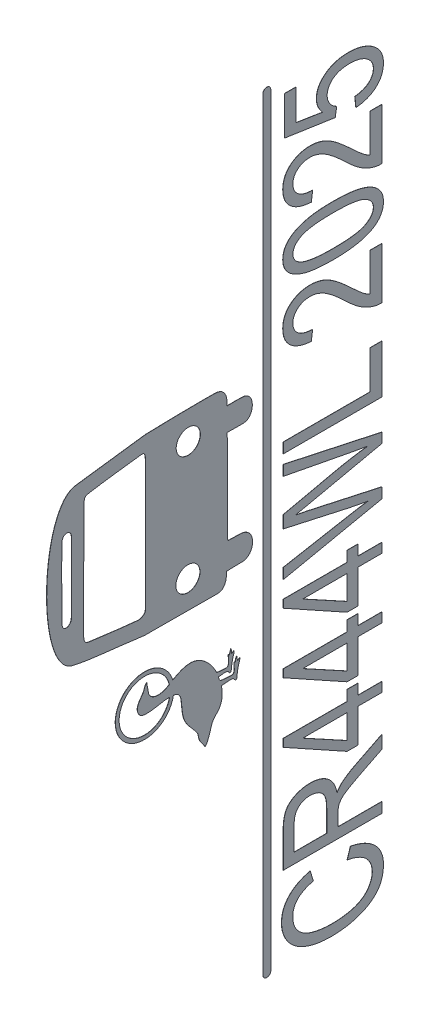
SolidWorks part; units mm, degrees
material "Blue Steel"
ref_plane "Front Plane" through (0, 0, 0) normal (1, 0, 0) x (0, 1, 0)
ref_plane "Top Plane" through (0, 0, 0) normal (0, 0, 1) x (0, 1, 0)
ref_plane "Right Plane" through (0, 0, 0) normal (0, 1, 0) x (-1, 0, 0)
sketch "Sketch3" plane through (0, 0, 0) normal (1, 0, 0) x (0, 1, 0)
  line L0 (443.7564, 375.9378) -> (444.3267, 377.8364)
  line L1 (444.3267, 377.8364) -> (445.1074, 379.6689)
  line L2 (445.1074, 379.6689) -> (446.0917, 381.4354)
  line L3 (446.0917, 381.4354) -> (447.2727, 383.1363)
  line L4 (447.2727, 383.1363) -> (448.6434, 384.7715)
  line L5 (448.6434, 384.7715) -> (450.197, 386.3415)
  line L6 (450.197, 386.3415) -> (451.9266, 387.8462)
  line L7 (451.9266, 387.8462) -> (453.8253, 389.2861)
  line L8 (453.8253, 389.2861) -> (458.1022, 391.9717)
  line L9 (458.1022, 391.9717) -> (462.9727, 394.3999)
  line L10 (462.9727, 394.3999) -> (468.3816, 396.5722)
  line L11 (468.3816, 396.5722) -> (474.2737, 398.4903)
  line L12 (474.2737, 398.4903) -> (480.5938, 400.1558)
  line L13 (480.5938, 400.1558) -> (487.2868, 401.5701)
  line L14 (487.2868, 401.5701) -> (494.2975, 402.7349)
  line L15 (494.2975, 402.7349) -> (501.5707, 403.6517)
  line L16 (501.5707, 403.6517) -> (509.0512, 404.3222)
  line L17 (509.0512, 404.3222) -> (516.684, 404.748)
  line L18 (516.684, 404.748) -> (524.4137, 404.9305)
  line L19 (524.4137, 404.9305) -> (532.1853, 404.8715)
  line L20 (532.1853, 404.8715) -> (539.9436, 404.5724)
  line L21 (539.9436, 404.5724) -> (547.6333, 404.0348)
  line L22 (547.6333, 404.0348) -> (555.1994, 403.2604)
  line L23 (555.1994, 403.2604) -> (562.5866, 402.2507)
  line L24 (562.5866, 402.2507) -> (569.7399, 401.0073)
  line L25 (569.7399, 401.0073) -> (576.6039, 399.5318)
  line L26 (576.6039, 399.5318) -> (583.1236, 397.8257)
  line L27 (583.1236, 397.8257) -> (589.2437, 395.8906)
  line L28 (589.2437, 395.8906) -> (594.9092, 393.7282)
  line L29 (594.9092, 393.7282) -> (600.0648, 391.34)
  line L30 (600.0648, 391.34) -> (604.6553, 388.7276)
  line L31 (604.6553, 388.7276) -> (608.6256, 385.8925)
  line L32 (608.6256, 385.8925) -> (610.361, 384.3919)
  line L33 (610.361, 384.3919) -> (611.9206, 382.8363)
  line L34 (611.9206, 382.8363) -> (613.2975, 381.2259)
  line L35 (613.2975, 381.2259) -> (614.485, 379.5607)
  line L36 (614.485, 379.5607) -> (615.476, 377.8411)
  line L37 (615.476, 377.8411) -> (616.2636, 376.0672)
  line L38 (616.2636, 376.0672) -> (616.8411, 374.2393)
  line L39 (616.8411, 374.2393) -> (617.2014, 372.3574)
  line L40 (617.2014, 372.3574) -> (627.5444, 294.1877)
  line L41 (627.5444, 294.1877) -> (627.8598, 282.2992)
  line L42 (627.8598, 282.2992) -> (628.4352, 255.656)
  line L43 (628.4352, 255.656) -> (628.7144, 227.7914)
  line L44 (628.7144, 227.7914) -> (628.5692, 217.6304)
  line L45 (628.5692, 217.6304) -> (628.395, 214.2328)
  line L46 (628.395, 214.2328) -> (628.1415, 212.239)
  line L47 (628.1415, 212.239) -> (627.4477, 210.125)
  line L48 (627.4477, 210.125) -> (626.4999, 208.3279)
  line L49 (626.4999, 208.3279) -> (625.3392, 206.8227)
  line L50 (625.3392, 206.8227) -> (624.007, 205.5845)
  line L51 (624.007, 205.5845) -> (622.5443, 204.5885)
  line L52 (622.5443, 204.5885) -> (620.9925, 203.8098)
  line L53 (620.9925, 203.8098) -> (619.3928, 203.2234)
  line L54 (619.3928, 203.2234) -> (617.7864, 202.8044)
  line L55 (617.7864, 202.8044) -> (614.7186, 202.3692)
  line L56 (614.7186, 202.3692) -> (612.1189, 202.305)
  line L57 (612.1189, 202.305) -> (609.6433, 202.4927)
  line L58 (609.6433, 202.4927) -> (609.6789, 195.5426)
  line L59 (609.6789, 195.5426) -> (609.6273, 189.5272)
  line L60 (609.6273, 189.5272) -> (609.4439, 184.1935)
  line L61 (609.4439, 184.1935) -> (609.0163, 181.7413)
  line L62 (609.0163, 181.7413) -> (608.1033, 179.6277)
  line L63 (608.1033, 179.6277) -> (606.7749, 177.8495)
  line L64 (606.7749, 177.8495) -> (605.1013, 176.4034)
  line L65 (605.1013, 176.4034) -> (603.1524, 175.2862)
  line L66 (603.1524, 175.2862) -> (600.9984, 174.4949)
  line L67 (600.9984, 174.4949) -> (598.7092, 174.0261)
  line L68 (598.7092, 174.0261) -> (596.355, 173.8767)
  line L69 (596.355, 173.8767) -> (594.0058, 174.0434)
  line L70 (594.0058, 174.0434) -> (591.7316, 174.5232)
  line L71 (591.7316, 174.5232) -> (589.6026, 175.3128)
  line L72 (589.6026, 175.3128) -> (587.6888, 176.4089)
  line L73 (587.6888, 176.4089) -> (586.0602, 177.8085)
  line L74 (586.0602, 177.8085) -> (584.7868, 179.5083)
  line L75 (584.7868, 179.5083) -> (583.9389, 181.5051)
  line L76 (583.9389, 181.5051) -> (583.5864, 183.7957)
  line L77 (583.5864, 183.7957) -> (583.6241, 194.8026)
  line L78 (583.6241, 194.8026) -> (583.7857, 202.0952)
  line L79 (583.7857, 202.0952) -> (477.9682, 201.4981)
  line L80 (477.9682, 201.4981) -> (477.5705, 187.376)
  line L81 (477.5705, 187.376) -> (477.451, 185.6859)
  line L82 (477.451, 185.6859) -> (477.1768, 184.1076)
  line L83 (477.1768, 184.1076) -> (476.7584, 182.6408)
  line L84 (476.7584, 182.6408) -> (476.2063, 181.285)
  line L85 (476.2063, 181.285) -> (475.5311, 180.0399)
  line L86 (475.5311, 180.0399) -> (474.7433, 178.905)
  line L87 (474.7433, 178.905) -> (472.8723, 176.9645)
  line L88 (472.8723, 176.9645) -> (470.6778, 175.4601)
  line L89 (470.6778, 175.4601) -> (468.2441, 174.3886)
  line L90 (468.2441, 174.3886) -> (465.6557, 173.7469)
  line L91 (465.6557, 173.7469) -> (462.9969, 173.5317)
  line L92 (462.9969, 173.5317) -> (460.3523, 173.7399)
  line L93 (460.3523, 173.7399) -> (457.8062, 174.3681)
  line L94 (457.8062, 174.3681) -> (455.443, 175.4131)
  line L95 (455.443, 175.4131) -> (453.3472, 176.8719)
  line L96 (453.3472, 176.8719) -> (451.6032, 178.741)
  line L97 (451.6032, 178.741) -> (450.8895, 179.8285)
  line L98 (450.8895, 179.8285) -> (450.2955, 181.0174)
  line L99 (450.2955, 181.0174) -> (449.8315, 182.3073)
  line L100 (449.8315, 182.3073) -> (449.5083, 183.6978)
  line L101 (449.5083, 183.6978) -> (449.3364, 185.1885)
  line L102 (449.3364, 185.1885) -> (449.3262, 186.7789)
  line L103 (449.3262, 186.7789) -> (449.1788, 195.9705)
  line L104 (449.1788, 195.9705) -> (448.9285, 202.8903)
  line L105 (448.9285, 202.8903) -> (446.3302, 202.8509)
  line L106 (446.3302, 202.8509) -> (443.665, 203.0542)
  line L107 (443.665, 203.0542) -> (440.6073, 203.6306)
  line L108 (440.6073, 203.6306) -> (439.0526, 204.1114)
  line L109 (439.0526, 204.1114) -> (437.5455, 204.7485)
  line L110 (437.5455, 204.7485) -> (436.1344, 205.5631)
  line L111 (436.1344, 205.5631) -> (434.8681, 206.5762)
  line L112 (434.8681, 206.5762) -> (433.7949, 207.8089)
  line L113 (433.7949, 207.8089) -> (432.9636, 209.2821)
  line L114 (432.9636, 209.2821) -> (432.4226, 211.0169)
  line L115 (432.4226, 211.0169) -> (432.2206, 213.0344)
  line L116 (432.2206, 213.0344) -> (432.6183, 295.182)
  line L117 (432.6183, 295.182) -> (435.9455, 321.5056)
  line L118 (435.9455, 321.5056) -> (438.4441, 342.9264)
  line L119 (438.4441, 342.9264) -> (439.6016, 352.1793)
  line L120 (439.6016, 352.1793) -> (440.8144, 360.6639)
  line L121 (440.8144, 360.6639) -> (442.1701, 368.5326)
  line L122 (442.1701, 368.5326) -> (443.7564, 375.9378)
  line L123 (463.4378, 259.8756) -> (461.4028, 259.7232)
  line L124 (461.4028, 259.7232) -> (459.4459, 259.2779)
  line L125 (459.4459, 259.2779) -> (457.594, 258.5579)
  line L126 (457.594, 258.5579) -> (455.8743, 257.5813)
  line L127 (455.8743, 257.5813) -> (454.3139, 256.3662)
  line L128 (454.3139, 256.3662) -> (452.94, 254.9308)
  line L129 (452.94, 254.9308) -> (451.7797, 253.2932)
  line L130 (451.7797, 253.2932) -> (450.8601, 251.4715)
  line L131 (450.8601, 251.4715) -> (450.2222, 249.5332)
  line L132 (450.2222, 249.5332) -> (449.8847, 247.5547)
  line L133 (449.8847, 247.5547) -> (449.8413, 245.5683)
  line L134 (449.8413, 245.5683) -> (450.0854, 243.6058)
  line L135 (450.0854, 243.6058) -> (450.6109, 241.6992)
  line L136 (450.6109, 241.6992) -> (451.4112, 239.8806)
  line L137 (451.4112, 239.8806) -> (452.4801, 238.1819)
  line L138 (452.4801, 238.1819) -> (453.8113, 236.6352)
  line L139 (453.8113, 236.6352) -> (455.358, 235.3041)
  line L140 (455.358, 235.3041) -> (457.0566, 234.2352)
  line L141 (457.0566, 234.2352) -> (458.8753, 233.4348)
  line L142 (458.8753, 233.4348) -> (460.7818, 232.9094)
  line L143 (460.7818, 232.9094) -> (462.7443, 232.6652)
  line L144 (462.7443, 232.6652) -> (464.7308, 232.7087)
  line L145 (464.7308, 232.7087) -> (466.7092, 233.0462)
  line L146 (466.7092, 233.0462) -> (468.6476, 233.6841)
  line L147 (468.6476, 233.6841) -> (470.4693, 234.6037)
  line L148 (470.4693, 234.6037) -> (472.1069, 235.764)
  line L149 (472.1069, 235.764) -> (473.5423, 237.1379)
  line L150 (473.5423, 237.1379) -> (474.7573, 238.6982)
  line L151 (474.7573, 238.6982) -> (475.7339, 240.4179)
  line L152 (475.7339, 240.4179) -> (476.4539, 242.2698)
  line L153 (476.4539, 242.2698) -> (476.8992, 244.2268)
  line L154 (476.8992, 244.2268) -> (477.0517, 246.2617)
  line L155 (477.0517, 246.2617) -> (476.7751, 249.0054)
  line L156 (476.7751, 249.0054) -> (475.9819, 251.5609)
  line L157 (475.9819, 251.5609) -> (474.7267, 253.8734)
  line L158 (474.7267, 253.8734) -> (473.0643, 255.8882)
  line L159 (473.0643, 255.8882) -> (471.0494, 257.5506)
  line L160 (471.0494, 257.5506) -> (468.7369, 258.8058)
  line L161 (468.7369, 258.8058) -> (466.1814, 259.5991)
  line L162 (466.1814, 259.5991) -> (463.4378, 259.8756)
  line L163 (597.0024, 259.4777) -> (594.9675, 259.3253)
  line L164 (594.9675, 259.3253) -> (593.0105, 258.88)
  line L165 (593.0105, 258.88) -> (591.1586, 258.16)
  line L166 (591.1586, 258.16) -> (589.4389, 257.1834)
  line L167 (589.4389, 257.1834) -> (587.8786, 255.9683)
  line L168 (587.8786, 255.9683) -> (586.5047, 254.5329)
  line L169 (586.5047, 254.5329) -> (585.3444, 252.8953)
  line L170 (585.3444, 252.8953) -> (584.4248, 251.0736)
  line L171 (584.4248, 251.0736) -> (583.7869, 249.1352)
  line L172 (583.7869, 249.1352) -> (583.4494, 247.1568)
  line L173 (583.4494, 247.1568) -> (583.4059, 245.1704)
  line L174 (583.4059, 245.1704) -> (583.6501, 243.2078)
  line L175 (583.6501, 243.2078) -> (584.1755, 241.3013)
  line L176 (584.1755, 241.3013) -> (584.9759, 239.4827)
  line L177 (584.9759, 239.4827) -> (586.0448, 237.784)
  line L178 (586.0448, 237.784) -> (587.3759, 236.2373)
  line L179 (587.3759, 236.2373) -> (588.9227, 234.9062)
  line L180 (588.9227, 234.9062) -> (590.6213, 233.8373)
  line L181 (590.6213, 233.8373) -> (592.4399, 233.0369)
  line L182 (592.4399, 233.0369) -> (594.3465, 232.5114)
  line L183 (594.3465, 232.5114) -> (596.309, 232.2673)
  line L184 (596.309, 232.2673) -> (598.2955, 232.3108)
  line L185 (598.2955, 232.3108) -> (600.2739, 232.6483)
  line L186 (600.2739, 232.6483) -> (602.2123, 233.2862)
  line L187 (602.2123, 233.2862) -> (604.034, 234.2057)
  line L188 (604.034, 234.2057) -> (605.6716, 235.366)
  line L189 (605.6716, 235.366) -> (607.107, 236.7399)
  line L190 (607.107, 236.7399) -> (608.322, 238.3003)
  line L191 (608.322, 238.3003) -> (609.2986, 240.02)
  line L192 (609.2986, 240.02) -> (610.0186, 241.8719)
  line L193 (610.0186, 241.8719) -> (610.4639, 243.8289)
  line L194 (610.4639, 243.8289) -> (610.6164, 245.8638)
  line L195 (610.6164, 245.8638) -> (610.3398, 248.6075)
  line L196 (610.3398, 248.6075) -> (609.5465, 251.1629)
  line L197 (609.5465, 251.1629) -> (608.2913, 253.4755)
  line L198 (608.2913, 253.4755) -> (606.6289, 255.4903)
  line L199 (606.6289, 255.4903) -> (604.6141, 257.1527)
  line L200 (604.6141, 257.1527) -> (602.3016, 258.4079)
  line L201 (602.3016, 258.4079) -> (599.7461, 259.2011)
  line L202 (599.7461, 259.2011) -> (597.0024, 259.4777)
  line L203 (466.0236, 363.4169) -> (463.7431, 363.278)
  line L204 (463.7431, 363.278) -> (461.9134, 362.9187)
  line L205 (461.9134, 362.9187) -> (460.4822, 362.3588)
  line L206 (460.4822, 362.3588) -> (459.3971, 361.6184)
  line L207 (459.3971, 361.6184) -> (458.6058, 360.7174)
  line L208 (458.6058, 360.7174) -> (458.0559, 359.6758)
  line L209 (458.0559, 359.6758) -> (457.695, 358.5136)
  line L210 (457.695, 358.5136) -> (457.4709, 357.2507)
  line L211 (457.4709, 357.2507) -> (453.2515, 324.2487)
  line L212 (453.2515, 324.2487) -> (450.9069, 302.5519)
  line L213 (450.9069, 302.5519) -> (450.9138, 301.2027)
  line L214 (450.9138, 301.2027) -> (451.1777, 299.7738)
  line L215 (451.1777, 299.7738) -> (451.6723, 298.3453)
  line L216 (451.6723, 298.3453) -> (452.3709, 296.9967)
  line L217 (452.3709, 296.9967) -> (453.247, 295.808)
  line L218 (453.247, 295.808) -> (454.2741, 294.859)
  line L219 (454.2741, 294.859) -> (455.4256, 294.2293)
  line L220 (455.4256, 294.2293) -> (456.675, 293.9989)
  line L221 (456.675, 293.9989) -> (531.4741, 293.7367)
  line L222 (531.4741, 293.7367) -> (568.3592, 293.7493)
  line L223 (568.3592, 293.7493) -> (603.8647, 293.9989)
  line L224 (603.8647, 293.9989) -> (605.9659, 294.1164)
  line L225 (605.9659, 294.1164) -> (607.5922, 294.4005)
  line L226 (607.5922, 294.4005) -> (608.798, 294.8365)
  line L227 (608.798, 294.8365) -> (609.638, 295.4094)
  line L228 (609.638, 295.4094) -> (610.1666, 296.1043)
  line L229 (610.1666, 296.1043) -> (610.4382, 296.9064)
  line L230 (610.4382, 296.9064) -> (610.5074, 297.8008)
  line L231 (610.5074, 297.8008) -> (610.4286, 298.7726)
  line L232 (610.4286, 298.7726) -> (606.7185, 327.9534)
  line L233 (606.7185, 327.9534) -> (604.6983, 342.9592)
  line L234 (604.6983, 342.9592) -> (602.4725, 357.2507)
  line L235 (602.4725, 357.2507) -> (601.7488, 359.9905)
  line L236 (601.7488, 359.9905) -> (601.2717, 360.9582)
  line L237 (601.2717, 360.9582) -> (600.7166, 361.6926)
  line L238 (600.7166, 361.6926) -> (600.0826, 362.2198)
  line L239 (600.0826, 362.2198) -> (599.3688, 362.566)
  line L240 (599.3688, 362.566) -> (597.6986, 362.8198)
  line L241 (597.6986, 362.8198) -> (531.888, 363.3934)
  line L242 (531.888, 363.3934) -> (498.9506, 363.5403)
  line L243 (498.9506, 363.5403) -> (466.0236, 363.4169)
  line L244 (489.8923, 387.6831) -> (488.3432, 387.5596)
  line L245 (488.3432, 387.5596) -> (487.0271, 387.2206)
  line L246 (487.0271, 387.2206) -> (485.9404, 386.6971)
  line L247 (485.9404, 386.6971) -> (485.0795, 386.0198)
  line L248 (485.0795, 386.0198) -> (484.4409, 385.2197)
  line L249 (484.4409, 385.2197) -> (484.0212, 384.3276)
  line L250 (484.0212, 384.3276) -> (483.8168, 383.3745)
  line L251 (483.8168, 383.3745) -> (483.8242, 382.3911)
  line L252 (483.8242, 382.3911) -> (484.0398, 381.4084)
  line L253 (484.0398, 381.4084) -> (484.4603, 380.4573)
  line L254 (484.4603, 380.4573) -> (485.082, 379.5685)
  line L255 (485.082, 379.5685) -> (485.9014, 378.7731)
  line L256 (485.9014, 378.7731) -> (486.915, 378.1018)
  line L257 (486.915, 378.1018) -> (488.1194, 377.5856)
  line L258 (488.1194, 377.5856) -> (489.511, 377.2552)
  line L259 (489.511, 377.2552) -> (491.0862, 377.1417)
  line L260 (491.0862, 377.1417) -> (569.8526, 377.1417)
  line L261 (569.8526, 377.1417) -> (571.2425, 377.2603)
  line L262 (571.2425, 377.2603) -> (572.4517, 377.5891)
  line L263 (572.4517, 377.5891) -> (573.4799, 378.0985)
  line L264 (573.4799, 378.0985) -> (574.3269, 378.7589)
  line L265 (574.3269, 378.7589) -> (574.9923, 379.5406)
  line L266 (574.9923, 379.5406) -> (575.4759, 380.4141)
  line L267 (575.4759, 380.4141) -> (575.7775, 381.3498)
  line L268 (575.7775, 381.3498) -> (575.8966, 382.318)
  line L269 (575.8966, 382.318) -> (575.833, 383.2892)
  line L270 (575.833, 383.2892) -> (575.5866, 384.2337)
  line L271 (575.5866, 384.2337) -> (575.1569, 385.1219)
  line L272 (575.1569, 385.1219) -> (574.5437, 385.9243)
  line L273 (574.5437, 385.9243) -> (573.7467, 386.6112)
  line L274 (573.7467, 386.6112) -> (572.7656, 387.1531)
  line L275 (572.7656, 387.1531) -> (571.6003, 387.5202)
  line L276 (571.6003, 387.5202) -> (570.2503, 387.6831)
  line L277 (570.2503, 387.6831) -> (550.2317, 388.0794)
  line L278 (550.2317, 388.0794) -> (529.537, 388.0572)
  line L279 (529.537, 388.0572) -> (489.8923, 387.6831)
  line L280 (385.5377, 292.4626) -> (383.3341, 292.1942)
  line L281 (383.3341, 292.1942) -> (381.1276, 291.7946)
  line L282 (381.1276, 291.7946) -> (376.7374, 290.9387)
  line L283 (376.7374, 290.9387) -> (374.4246, 290.5942)
  line L284 (374.4246, 290.5942) -> (373.2896, 290.3186)
  line L285 (373.2896, 290.3186) -> (372.2244, 289.8607)
  line L286 (372.2244, 289.8607) -> (370.326, 288.4911)
  line L287 (370.326, 288.4911) -> (368.8743, 286.8432)
  line L288 (368.8743, 286.8432) -> (367.8344, 284.9721)
  line L289 (367.8344, 284.9721) -> (367.1712, 282.9324)
  line L290 (367.1712, 282.9324) -> (366.8494, 280.7791)
  line L291 (366.8494, 280.7791) -> (366.8341, 278.567)
  line L292 (366.8341, 278.567) -> (367.0902, 276.351)
  line L293 (367.0902, 276.351) -> (367.5824, 274.1858)
  line L294 (367.5824, 274.1858) -> (368.7795, 271.0126)
  line L295 (368.7795, 271.0126) -> (370.3949, 267.93)
  line L296 (370.3949, 267.93) -> (373.9339, 262.0008)
  line L297 (373.9339, 262.0008) -> (375.5273, 259.0483)
  line L298 (375.5273, 259.0483) -> (376.9689, 256.028)
  line L299 (376.9689, 256.028) -> (378.1946, 252.9443)
  line L300 (378.1946, 252.9443) -> (379.1403, 249.8016)
  line L301 (379.1403, 249.8016) -> (379.742, 246.6042)
  line L302 (379.742, 246.6042) -> (379.9356, 243.3567)
  line L303 (379.9356, 243.3567) -> (379.6571, 240.0632)
  line L304 (379.6571, 240.0632) -> (378.8425, 236.7283)
  line L305 (378.8425, 236.7283) -> (377.8247, 234.1419)
  line L306 (377.8247, 234.1419) -> (376.5291, 231.6542)
  line L307 (376.5291, 231.6542) -> (374.9929, 229.2747)
  line L308 (374.9929, 229.2747) -> (373.2533, 227.0126)
  line L309 (373.2533, 227.0126) -> (371.3474, 224.8775)
  line L310 (371.3474, 224.8775) -> (369.3124, 222.8786)
  line L311 (369.3124, 222.8786) -> (367.1855, 221.0255)
  line L312 (367.1855, 221.0255) -> (365.0038, 219.3274)
  line L313 (365.0038, 219.3274) -> (361.8149, 217.1483)
  line L314 (361.8149, 217.1483) -> (358.4599, 215.2369)
  line L315 (358.4599, 215.2369) -> (356.8237, 214.4179)
  line L316 (356.8237, 214.4179) -> (356.156, 213.8429)
  line L317 (356.156, 213.8429) -> (355.7823, 213.0319)
  line L318 (355.7823, 213.0319) -> (355.3023, 208.9825)
  line L319 (355.3023, 208.9825) -> (355.0544, 204.9121)
  line L320 (355.0544, 204.9121) -> (354.9667, 203.0412)
  line L321 (354.9667, 203.0412) -> (355.1844, 202.1756)
  line L322 (355.1844, 202.1756) -> (355.7837, 201.4177)
  line L323 (355.7837, 201.4177) -> (356.8056, 200.8556)
  line L324 (356.8056, 200.8556) -> (358.0847, 200.5487)
  line L325 (358.0847, 200.5487) -> (359.5432, 200.4395)
  line L326 (359.5432, 200.4395) -> (361.1035, 200.4706)
  line L327 (361.1035, 200.4706) -> (364.2185, 200.7242)
  line L328 (364.2185, 200.7242) -> (366.8078, 200.8501)
  line L329 (366.8078, 200.8501) -> (366.1301, 199.722)
  line L330 (366.1301, 199.722) -> (366.1301, 199.4961)
  line L331 (366.1301, 199.4961) -> (371.0943, 198.142)
  line L332 (371.0943, 198.142) -> (371.0943, 197.6902)
  line L333 (371.0943, 197.6902) -> (365.9045, 197.0139)
  line L334 (365.9045, 197.0139) -> (367.9352, 194.3062)
  line L335 (367.9352, 194.3062) -> (366.5198, 194.3394)
  line L336 (366.5198, 194.3394) -> (365.0861, 194.6352)
  line L337 (365.0861, 194.6352) -> (362.2942, 195.4609)
  line L338 (362.2942, 195.4609) -> (357.5842, 196.5628)
  line L339 (357.5842, 196.5628) -> (352.817, 197.3698)
  line L340 (352.817, 197.3698) -> (350.3183, 197.5179)
  line L341 (350.3183, 197.5179) -> (349.0085, 197.7953)
  line L342 (349.0085, 197.7953) -> (348.5393, 198.0575)
  line L343 (348.5393, 198.0575) -> (348.2704, 198.4296)
  line L344 (348.2704, 198.4296) -> (348.2334, 198.9424)
  line L345 (348.2334, 198.9424) -> (348.4497, 199.4085)
  line L346 (348.4497, 199.4085) -> (349.3594, 200.2542)
  line L347 (349.3594, 200.2542) -> (350.434, 201.0749)
  line L348 (350.434, 201.0749) -> (350.8565, 201.5097)
  line L349 (350.8565, 201.5097) -> (351.1082, 201.9788)
  line L350 (351.1082, 201.9788) -> (351.3417, 203.1302)
  line L351 (351.3417, 203.1302) -> (351.422, 204.3498)
  line L352 (351.422, 204.3498) -> (351.2729, 206.9081)
  line L353 (351.2729, 206.9081) -> (350.9609, 209.4837)
  line L354 (350.9609, 209.4837) -> (350.786, 211.9064)
  line L355 (350.786, 211.9064) -> (348.3421, 211.2676)
  line L356 (348.3421, 211.2676) -> (347.1133, 210.7444)
  line L357 (347.1133, 210.7444) -> (346.2412, 210.0385)
  line L358 (346.2412, 210.0385) -> (345.8875, 209.3066)
  line L359 (345.8875, 209.3066) -> (345.7111, 208.4385)
  line L360 (345.7111, 208.4385) -> (345.5607, 206.7166)
  line L361 (345.5607, 206.7166) -> (344.855, 198.8189)
  line L362 (344.855, 198.8189) -> (344.7323, 196.9489)
  line L363 (344.7323, 196.9489) -> (344.9205, 196.0594)
  line L364 (344.9205, 196.0594) -> (345.4337, 195.2601)
  line L365 (345.4337, 195.2601) -> (346.3337, 194.6301)
  line L366 (346.3337, 194.6301) -> (347.4636, 194.2754)
  line L367 (347.4636, 194.2754) -> (348.7561, 194.1353)
  line L368 (348.7561, 194.1353) -> (350.1437, 194.149)
  line L369 (350.1437, 194.149) -> (352.9349, 194.3951)
  line L370 (352.9349, 194.3951) -> (355.2983, 194.528)
  line L371 (355.2983, 194.528) -> (356.0026, 194.3833)
  line L372 (356.0026, 194.3833) -> (356.3461, 194.0716)
  line L373 (356.3461, 194.0716) -> (356.2786, 193.6506)
  line L374 (356.2786, 193.6506) -> (355.7501, 193.1781)
  line L375 (355.7501, 193.1781) -> (355.7501, 192.9522)
  line L376 (355.7501, 192.9522) -> (357.1045, 192.8746)
  line L377 (357.1045, 192.8746) -> (358.5318, 192.6345)
  line L378 (358.5318, 192.6345) -> (359.8658, 192.1584)
  line L379 (359.8658, 192.1584) -> (360.94, 191.3727)
  line L380 (360.94, 191.3727) -> (355.7501, 190.4704)
  line L381 (355.7501, 190.4704) -> (357.7809, 187.9882)
  line L382 (357.7809, 187.9882) -> (356.36, 187.9361)
  line L383 (356.36, 187.9361) -> (354.8293, 188.2265)
  line L384 (354.8293, 188.2265) -> (351.914, 189.1164)
  line L385 (351.914, 189.1164) -> (347.3232, 190.2324)
  line L386 (347.3232, 190.2324) -> (342.6626, 190.9858)
  line L387 (342.6626, 190.9858) -> (340.1383, 191.1408)
  line L388 (340.1383, 191.1408) -> (338.8188, 191.4382)
  line L389 (338.8188, 191.4382) -> (338.3493, 191.7134)
  line L390 (338.3493, 191.7134) -> (338.0847, 192.1)
  line L391 (338.0847, 192.1) -> (338.0686, 192.6074)
  line L392 (338.0686, 192.6074) -> (338.3089, 193.0802)
  line L393 (338.3089, 193.0802) -> (339.2637, 193.9718)
  line L394 (339.2637, 193.9718) -> (340.3592, 194.8739)
  line L395 (340.3592, 194.8739) -> (340.7754, 195.3598)
  line L396 (340.7754, 195.3598) -> (341.0054, 195.8856)
  line L397 (341.0054, 195.8856) -> (341.2095, 197.3605)
  line L398 (341.2095, 197.3605) -> (341.263, 198.9176)
  line L399 (341.263, 198.9176) -> (341.0596, 202.1738)
  line L400 (341.0596, 202.1738) -> (340.6793, 205.4449)
  line L401 (340.6793, 205.4449) -> (340.4058, 208.5216)
  line L402 (340.4058, 208.5216) -> (335.0557, 207.9072)
  line L403 (335.0557, 207.9072) -> (332.4589, 207.7725)
  line L404 (332.4589, 207.7725) -> (329.9014, 207.824)
  line L405 (329.9014, 207.824) -> (327.3736, 208.1153)
  line L406 (327.3736, 208.1153) -> (324.8659, 208.6997)
  line L407 (324.8659, 208.6997) -> (322.3685, 209.6307)
  line L408 (322.3685, 209.6307) -> (319.8719, 210.9618)
  line L409 (319.8719, 210.9618) -> (318.4041, 211.9904)
  line L410 (318.4041, 211.9904) -> (317.0506, 213.1306)
  line L411 (317.0506, 213.1306) -> (314.4909, 215.5338)
  line L412 (314.4909, 215.5338) -> (313.1867, 216.6906)
  line L413 (313.1867, 216.6906) -> (311.8011, 217.747)
  line L414 (311.8011, 217.747) -> (310.285, 218.6499)
  line L415 (310.285, 218.6499) -> (308.5896, 219.3462)
  line L416 (308.5896, 219.3462) -> (301.7659, 221.5106)
  line L417 (301.7659, 221.5106) -> (298.3904, 222.6784)
  line L418 (298.3904, 222.6784) -> (295.0507, 223.9963)
  line L419 (295.0507, 223.9963) -> (292.3771, 225.1331)
  line L420 (292.3771, 225.1331) -> (291.1751, 225.9285)
  line L421 (291.1751, 225.9285) -> (290.3121, 227.0247)
  line L422 (290.3121, 227.0247) -> (292.7175, 228.5351)
  line L423 (292.7175, 228.5351) -> (294.9868, 230.2245)
  line L424 (294.9868, 230.2245) -> (297.2882, 231.8759)
  line L425 (297.2882, 231.8759) -> (299.7893, 233.2725)
  line L426 (299.7893, 233.2725) -> (302.0378, 233.9956)
  line L427 (302.0378, 233.9956) -> (304.2804, 234.4244)
  line L428 (304.2804, 234.4244) -> (306.4776, 234.9724)
  line L429 (306.4776, 234.9724) -> (307.5467, 235.4203)
  line L430 (307.5467, 235.4203) -> (308.5896, 236.0532)
  line L431 (308.5896, 236.0532) -> (311.1554, 238.0276)
  line L432 (311.1554, 238.0276) -> (313.6615, 240.1282)
  line L433 (313.6615, 240.1282) -> (318.6631, 244.3952)
  line L434 (318.6631, 244.3952) -> (321.2427, 246.405)
  line L435 (321.2427, 246.405) -> (323.9307, 248.228)
  line L436 (323.9307, 248.228) -> (326.7692, 249.786)
  line L437 (326.7692, 249.786) -> (329.8003, 251.0007)
  line L438 (329.8003, 251.0007) -> (334.0602, 252.0858)
  line L439 (334.0602, 252.0858) -> (338.4119, 252.7537)
  line L440 (338.4119, 252.7537) -> (347.1752, 253.6137)
  line L441 (347.1752, 253.6137) -> (349.8193, 253.9578)
  line L442 (349.8193, 253.9578) -> (352.3295, 254.5873)
  line L443 (352.3295, 254.5873) -> (353.4944, 255.088)
  line L444 (353.4944, 255.088) -> (354.578, 255.7548)
  line L445 (354.578, 255.7548) -> (355.5641, 256.6192)
  line L446 (355.5641, 256.6192) -> (356.4369, 257.7128)
  line L447 (356.4369, 257.7128) -> (357.064, 258.7977)
  line L448 (357.064, 258.7977) -> (357.5465, 259.9261)
  line L449 (357.5465, 259.9261) -> (358.153, 262.2836)
  line L450 (358.153, 262.2836) -> (358.4066, 264.7249)
  line L451 (358.4066, 264.7249) -> (358.4577, 267.19)
  line L452 (358.4577, 267.19) -> (358.3445, 269.9645)
  line L453 (358.3445, 269.9645) -> (358.0438, 272.7298)
  line L454 (358.0438, 272.7298) -> (357.1092, 278.2449)
  line L455 (357.1092, 278.2449) -> (356.1132, 283.761)
  line L456 (356.1132, 283.761) -> (355.7358, 286.5273)
  line L457 (355.7358, 286.5273) -> (355.5153, 289.3034)
  line L458 (355.5153, 289.3034) -> (355.4027, 292.2136)
  line L459 (355.4027, 292.2136) -> (355.5329, 295.2148)
  line L460 (355.5329, 295.2148) -> (355.7928, 296.6735)
  line L461 (355.7928, 296.6735) -> (356.2376, 298.0638)
  line L462 (356.2376, 298.0638) -> (356.9091, 299.3554)
  line L463 (356.9091, 299.3554) -> (357.8485, 300.5178)
  line L464 (357.8485, 300.5178) -> (359.2925, 301.6308)
  line L465 (359.2925, 301.6308) -> (360.9397, 302.4189)
  line L466 (360.9397, 302.4189) -> (362.2611, 302.8282)
  line L467 (362.2611, 302.8282) -> (363.5174, 303.059)
  line L468 (363.5174, 303.059) -> (364.7154, 303.1269)
  line L469 (364.7154, 303.1269) -> (365.862, 303.0474)
  line L470 (365.862, 303.0474) -> (368.0281, 302.5086)
  line L471 (368.0281, 302.5086) -> (370.0701, 301.5673)
  line L472 (370.0701, 301.5673) -> (372.0427, 300.3482)
  line L473 (372.0427, 300.3482) -> (374.0003, 298.9759)
  line L474 (374.0003, 298.9759) -> (375.9975, 297.575)
  line L475 (375.9975, 297.575) -> (378.0889, 296.2703)
  line L476 (378.0889, 296.2703) -> (379.9753, 295.4959)
  line L477 (379.9753, 295.4959) -> (382.173, 294.7707)
  line L478 (382.173, 294.7707) -> (384.1903, 293.8432)
  line L479 (384.1903, 293.8432) -> (384.9776, 293.2252)
  line L480 (384.9776, 293.2252) -> (385.5353, 292.4624)
  line L481 (385.5353, 292.4624) -> (385.5377, 292.4626)
  line L482 (100.1503, 67.2217) -> (111.6816, 63.5229)
  line L483 (111.6816, 63.5229) -> (110.6841, 59.1459)
  line L484 (110.6841, 59.1459) -> (109.5046, 55.0355)
  line L485 (109.5046, 55.0355) -> (108.1431, 51.1917)
  line L486 (108.1431, 51.1917) -> (106.5995, 47.6144)
  line L487 (106.5995, 47.6144) -> (104.8739, 44.3036)
  line L488 (104.8739, 44.3036) -> (102.9662, 41.2594)
  line L489 (102.9662, 41.2594) -> (100.8766, 38.4818)
  line L490 (100.8766, 38.4818) -> (98.6048, 35.9707)
  line L491 (98.6048, 35.9707) -> (96.191, 33.7592)
  line L492 (96.191, 33.7592) -> (93.6453, 31.8426)
  line L493 (93.6453, 31.8426) -> (90.9677, 30.2208)
  line L494 (90.9677, 30.2208) -> (88.1583, 28.8939)
  line L495 (88.1583, 28.8939) -> (85.2169, 27.8619)
  line L496 (85.2169, 27.8619) -> (82.1437, 27.1248)
  line L497 (82.1437, 27.1248) -> (78.9386, 26.6825)
  line L498 (78.9386, 26.6825) -> (75.6016, 26.535)
  line L499 (75.6016, 26.535) -> (72.1615, 26.6483)
  line L500 (72.1615, 26.6483) -> (68.8849, 26.9879)
  line L501 (68.8849, 26.9879) -> (65.7717, 27.5541)
  line L502 (65.7717, 27.5541) -> (62.822, 28.3467)
  line L503 (62.822, 28.3467) -> (60.0357, 29.3657)
  line L504 (60.0357, 29.3657) -> (57.4129, 30.6112)
  line L505 (57.4129, 30.6112) -> (54.9536, 32.0832)
  line L506 (54.9536, 32.0832) -> (52.6577, 33.7816)
  line L507 (52.6577, 33.7816) -> (50.5235, 35.7136)
  line L508 (50.5235, 35.7136) -> (48.5192, 37.8484)
  line L509 (48.5192, 37.8484) -> (46.645, 40.1861)
  line L510 (46.645, 40.1861) -> (44.9008, 42.7267)
  line L511 (44.9008, 42.7267) -> (43.2867, 45.4701)
  line L512 (43.2867, 45.4701) -> (41.8025, 48.4164)
  line L513 (41.8025, 48.4164) -> (40.4484, 51.5655)
  line L514 (40.4484, 51.5655) -> (39.2243, 54.9176)
  line L515 (39.2243, 54.9176) -> (38.1516, 58.4029)
  line L516 (38.1516, 58.4029) -> (37.2219, 61.9519)
  line L517 (37.2219, 61.9519) -> (36.4353, 65.5646)
  line L518 (36.4353, 65.5646) -> (35.7917, 69.2409)
  line L519 (35.7917, 69.2409) -> (34.9335, 76.7848)
  line L520 (34.9335, 76.7848) -> (34.6474, 84.5834)
  line L521 (34.6474, 84.5834) -> (34.7282, 88.8353)
  line L522 (34.7282, 88.8353) -> (34.9706, 92.9481)
  line L523 (34.9706, 92.9481) -> (35.3746, 96.9217)
  line L524 (35.3746, 96.9217) -> (35.9403, 100.7561)
  line L525 (35.9403, 100.7561) -> (36.6675, 104.4514)
  line L526 (36.6675, 104.4514) -> (37.5563, 108.0075)
  line L527 (37.5563, 108.0075) -> (38.6067, 111.4243)
  line L528 (38.6067, 111.4243) -> (39.8187, 114.7021)
  line L529 (39.8187, 114.7021) -> (41.1942, 117.8312)
  line L530 (41.1942, 117.8312) -> (42.7053, 120.7645)
  line L531 (42.7053, 120.7645) -> (44.3519, 123.502)
  line L532 (44.3519, 123.502) -> (46.1342, 126.0438)
  line L533 (46.1342, 126.0438) -> (48.0521, 128.3897)
  line L534 (48.0521, 128.3897) -> (50.1055, 130.5399)
  line L535 (50.1055, 130.5399) -> (52.2946, 132.4942)
  line L536 (52.2946, 132.4942) -> (54.6193, 134.2528)
  line L537 (54.6193, 134.2528) -> (57.0563, 135.8274)
  line L538 (57.0563, 135.8274) -> (59.5528, 137.192)
  line L539 (59.5528, 137.192) -> (62.1087, 138.3467)
  line L540 (62.1087, 138.3467) -> (64.7241, 139.2915)
  line L541 (64.7241, 139.2915) -> (67.3989, 140.0263)
  line L542 (67.3989, 140.0263) -> (70.1331, 140.5511)
  line L543 (70.1331, 140.5511) -> (72.9268, 140.866)
  line L544 (72.9268, 140.866) -> (75.7799, 140.971)
  line L545 (75.7799, 140.971) -> (78.9841, 140.8389)
  line L546 (78.9841, 140.8389) -> (82.0582, 140.4426)
  line L547 (82.0582, 140.4426) -> (85.0024, 139.7821)
  line L548 (85.0024, 139.7821) -> (87.8165, 138.8574)
  line L549 (87.8165, 138.8574) -> (90.5006, 137.6685)
  line L550 (90.5006, 137.6685) -> (93.0546, 136.2154)
  line L551 (93.0546, 136.2154) -> (95.4787, 134.4981)
  line L552 (95.4787, 134.4981) -> (97.7727, 132.5166)
  line L553 (97.7727, 132.5166) -> (99.9172, 130.2957)
  line L554 (99.9172, 130.2957) -> (101.8926, 127.8601)
  line L555 (101.8926, 127.8601) -> (103.699, 125.2099)
  line L556 (103.699, 125.2099) -> (105.3364, 122.345)
  line L557 (105.3364, 122.345) -> (106.8048, 119.2654)
  line L558 (106.8048, 119.2654) -> (108.1041, 115.9712)
  line L559 (108.1041, 115.9712) -> (109.2344, 112.4623)
  line L560 (109.2344, 112.4623) -> (110.1956, 108.7387)
  line L561 (110.1956, 108.7387) -> (98.8426, 105.3419)
  line L562 (98.8426, 105.3419) -> (97.156, 110.9703)
  line L563 (97.156, 110.9703) -> (96.1845, 113.4766)
  line L564 (96.1845, 113.4766) -> (95.1276, 115.7777)
  line L565 (95.1276, 115.7777) -> (93.9852, 117.8736)
  line L566 (93.9852, 117.8736) -> (92.7574, 119.7643)
  line L567 (92.7574, 119.7643) -> (91.4442, 121.4498)
  line L568 (91.4442, 121.4498) -> (90.0455, 122.93)
  line L569 (90.0455, 122.93) -> (88.5576, 124.2215)
  line L570 (88.5576, 124.2215) -> (86.9769, 125.3408)
  line L571 (86.9769, 125.3408) -> (85.3033, 126.2879)
  line L572 (85.3033, 126.2879) -> (83.5368, 127.0628)
  line L573 (83.5368, 127.0628) -> (81.6774, 127.6655)
  line L574 (81.6774, 127.6655) -> (79.7252, 128.096)
  line L575 (79.7252, 128.096) -> (77.6801, 128.3543)
  line L576 (77.6801, 128.3543) -> (75.5421, 128.4404)
  line L577 (75.5421, 128.4404) -> (73.0819, 128.3449)
  line L578 (73.0819, 128.3449) -> (70.7238, 128.0583)
  line L579 (70.7238, 128.0583) -> (68.4678, 127.5806)
  line L580 (68.4678, 127.5806) -> (66.3141, 126.9118)
  line L581 (66.3141, 126.9118) -> (64.2625, 126.052)
  line L582 (64.2625, 126.052) -> (62.313, 125.0011)
  line L583 (62.313, 125.0011) -> (60.4657, 123.7591)
  line L584 (60.4657, 123.7591) -> (58.7206, 122.3261)
  line L585 (58.7206, 122.3261) -> (57.1037, 120.7315)
  line L586 (57.1037, 120.7315) -> (55.6112, 119.0047)
  line L587 (55.6112, 119.0047) -> (54.2431, 117.1459)
  line L588 (54.2431, 117.1459) -> (52.9995, 115.155)
  line L589 (52.9995, 115.155) -> (51.8804, 113.032)
  line L590 (51.8804, 113.032) -> (50.8857, 110.7768)
  line L591 (50.8857, 110.7768) -> (50.0155, 108.3896)
  line L592 (50.0155, 108.3896) -> (49.2697, 105.8703)
  line L593 (49.2697, 105.8703) -> (48.0734, 100.6948)
  line L594 (48.0734, 100.6948) -> (47.219, 95.4344)
  line L595 (47.219, 95.4344) -> (46.7063, 90.0891)
  line L596 (46.7063, 90.0891) -> (46.5354, 84.6588)
  line L597 (46.5354, 84.6588) -> (46.736, 77.8227)
  line L598 (46.736, 77.8227) -> (47.3379, 71.43)
  line L599 (47.3379, 71.43) -> (48.3409, 65.4808)
  line L600 (48.3409, 65.4808) -> (49.7452, 59.9751)
  line L601 (49.7452, 59.9751) -> (50.6182, 57.4345)
  line L602 (50.6182, 57.4345) -> (51.6027, 55.0591)
  line L603 (51.6027, 55.0591) -> (52.6986, 52.8488)
  line L604 (52.6986, 52.8488) -> (53.906, 50.8036)
  line L605 (53.906, 50.8036) -> (55.2248, 48.9235)
  line L606 (55.2248, 48.9235) -> (56.6551, 47.2086)
  line L607 (56.6551, 47.2086) -> (58.1968, 45.6588)
  line L608 (58.1968, 45.6588) -> (59.85, 44.2741)
  line L609 (59.85, 44.2741) -> (61.5765, 43.0534)
  line L610 (61.5765, 43.0534) -> (63.3384, 41.9954)
  line L611 (63.3384, 41.9954) -> (65.1355, 41.1002)
  line L612 (65.1355, 41.1002) -> (66.9679, 40.3677)
  line L613 (66.9679, 40.3677) -> (68.8356, 39.7981)
  line L614 (68.8356, 39.7981) -> (70.7386, 39.3912)
  line L615 (70.7386, 39.3912) -> (72.6769, 39.147)
  line L616 (72.6769, 39.147) -> (74.6505, 39.0656)
  line L617 (74.6505, 39.0656) -> (77.0263, 39.1765)
  line L618 (77.0263, 39.1765) -> (79.3091, 39.5091)
  line L619 (79.3091, 39.5091) -> (81.4991, 40.0634)
  line L620 (81.4991, 40.0634) -> (83.5962, 40.8395)
  line L621 (83.5962, 40.8395) -> (85.6005, 41.8374)
  line L622 (85.6005, 41.8374) -> (87.5118, 43.0569)
  line L623 (87.5118, 43.0569) -> (89.3303, 44.4982)
  line L624 (89.3303, 44.4982) -> (91.056, 46.1613)
  line L625 (91.056, 46.1613) -> (92.6673, 48.0425)
  line L626 (92.6673, 48.0425) -> (94.1431, 50.1384)
  line L627 (94.1431, 50.1384) -> (95.4833, 52.449)
  line L628 (95.4833, 52.449) -> (96.6879, 54.9742)
  line L629 (96.6879, 54.9742) -> (97.7569, 57.7141)
  line L630 (97.7569, 57.7141) -> (98.6903, 60.6686)
  line L631 (98.6903, 60.6686) -> (99.4881, 63.8378)
  line L632 (99.4881, 63.8378) -> (100.1503, 67.2217)
  line L633 (126.0661, 28.4222) -> (126.0661, 139.0839)
  line L634 (126.0661, 139.0839) -> (164.7021, 139.0839)
  line L635 (164.7021, 139.0839) -> (170.178, 138.8952)
  line L636 (170.178, 138.8952) -> (174.9555, 138.329)
  line L637 (174.9555, 138.329) -> (179.0345, 137.3855)
  line L638 (179.0345, 137.3855) -> (180.8122, 136.7721)
  line L639 (180.8122, 136.7721) -> (182.4152, 136.0645)
  line L640 (182.4152, 136.0645) -> (183.8928, 135.2565)
  line L641 (183.8928, 135.2565) -> (185.2943, 134.3047)
  line L642 (185.2943, 134.3047) -> (186.6196, 133.209)
  line L643 (186.6196, 133.209) -> (187.8688, 131.9694)
  line L644 (187.8688, 131.9694) -> (190.1387, 129.0585)
  line L645 (190.1387, 129.0585) -> (192.1039, 125.572)
  line L646 (192.1039, 125.572) -> (193.6902, 121.6986)
  line L647 (193.6902, 121.6986) -> (194.8233, 117.6271)
  line L648 (194.8233, 117.6271) -> (195.5031, 113.3575)
  line L649 (195.5031, 113.3575) -> (195.7297, 108.8897)
  line L650 (195.7297, 108.8897) -> (195.6359, 106.0035)
  line L651 (195.6359, 106.0035) -> (195.3545, 103.233)
  line L652 (195.3545, 103.233) -> (194.8855, 100.578)
  line L653 (194.8855, 100.578) -> (194.2289, 98.0386)
  line L654 (194.2289, 98.0386) -> (193.3846, 95.6149)
  line L655 (193.3846, 95.6149) -> (192.3528, 93.3067)
  line L656 (192.3528, 93.3067) -> (191.1333, 91.114)
  line L657 (191.1333, 91.114) -> (189.7263, 89.037)
  line L658 (189.7263, 89.037) -> (188.1233, 87.1098)
  line L659 (188.1233, 87.1098) -> (186.3159, 85.3665)
  line L660 (186.3159, 85.3665) -> (184.3042, 83.8073)
  line L661 (184.3042, 83.8073) -> (182.0883, 82.432)
  line L662 (182.0883, 82.432) -> (179.6679, 81.2408)
  line L663 (179.6679, 81.2408) -> (177.0433, 80.2335)
  line L664 (177.0433, 80.2335) -> (174.2143, 79.4102)
  line L665 (174.2143, 79.4102) -> (171.181, 78.771)
  line L666 (171.181, 78.771) -> (175.2081, 75.9969)
  line L667 (175.2081, 75.9969) -> (176.8092, 74.624)
  line L668 (176.8092, 74.624) -> (178.1355, 73.2605)
  line L669 (178.1355, 73.2605) -> (180.6283, 70.1326)
  line L670 (180.6283, 70.1326) -> (183.0542, 66.6367)
  line L671 (183.0542, 66.6367) -> (185.4132, 62.7728)
  line L672 (185.4132, 62.7728) -> (187.7053, 58.5409)
  line L673 (187.7053, 58.5409) -> (202.8625, 28.4222)
  line L674 (202.8625, 28.4222) -> (188.3592, 28.4222)
  line L675 (188.3592, 28.4222) -> (176.8278, 51.4452)
  line L676 (176.8278, 51.4452) -> (172.2212, 60.2393)
  line L677 (172.2212, 60.2393) -> (168.5062, 66.6933)
  line L678 (168.5062, 66.6933) -> (166.9125, 69.1371)
  line L679 (166.9125, 69.1371) -> (165.4005, 71.1847)
  line L680 (165.4005, 71.1847) -> (163.9702, 72.8359)
  line L681 (163.9702, 72.8359) -> (162.6217, 74.0909)
  line L682 (162.6217, 74.0909) -> (160.036, 75.8837)
  line L683 (160.036, 75.8837) -> (158.7209, 76.5394)
  line L684 (158.7209, 76.5394) -> (157.391, 77.0348)
  line L685 (157.391, 77.0348) -> (154.8053, 77.4311)
  line L686 (154.8053, 77.4311) -> (150.9714, 77.5632)
  line L687 (150.9714, 77.5632) -> (137.5974, 77.5632)
  line L688 (137.5974, 77.5632) -> (137.5974, 28.4222)
  line L689 (137.5974, 28.4222) -> (126.0661, 28.4222)
  line L690 (137.5974, 90.2448) -> (162.3839, 90.2448)
  line L691 (162.3839, 90.2448) -> (166.1212, 90.3722)
  line L692 (166.1212, 90.3722) -> (169.4275, 90.7543)
  line L693 (169.4275, 90.7543) -> (172.303, 91.3912)
  line L694 (172.303, 91.3912) -> (174.7474, 92.2829)
  line L695 (174.7474, 92.2829) -> (176.8427, 93.4907)
  line L696 (176.8427, 93.4907) -> (178.6705, 95.0004)
  line L697 (178.6705, 95.0004) -> (180.2308, 96.812)
  line L698 (180.2308, 96.812) -> (181.5236, 98.9256)
  line L699 (181.5236, 98.9256) -> (182.5378, 101.2751)
  line L700 (182.5378, 101.2751) -> (183.2622, 103.7189)
  line L701 (183.2622, 103.7189) -> (183.6968, 106.2571)
  line L702 (183.6968, 106.2571) -> (183.8417, 108.8897)
  line L703 (183.8417, 108.8897) -> (183.5594, 112.6404)
  line L704 (183.5594, 112.6404) -> (183.2065, 114.3848)
  line L705 (183.2065, 114.3848) -> (182.7124, 116.0419)
  line L706 (182.7124, 116.0419) -> (182.0771, 117.6118)
  line L707 (182.0771, 117.6118) -> (181.3007, 119.0944)
  line L708 (181.3007, 119.0944) -> (180.3831, 120.4897)
  line L709 (180.3831, 120.4897) -> (179.3243, 121.7977)
  line L710 (179.3243, 121.7977) -> (178.1281, 122.9831)
  line L711 (178.1281, 122.9831) -> (176.7684, 124.0104)
  line L712 (176.7684, 124.0104) -> (175.2452, 124.8796)
  line L713 (175.2452, 124.8796) -> (173.5586, 125.5908)
  line L714 (173.5586, 125.5908) -> (171.7086, 126.144)
  line L715 (171.7086, 126.144) -> (169.695, 126.5391)
  line L716 (169.695, 126.5391) -> (167.518, 126.7762)
  line L717 (167.518, 126.7762) -> (165.1776, 126.8552)
  line L718 (165.1776, 126.8552) -> (137.5974, 126.8552)
  line L719 (137.5974, 126.8552) -> (137.5974, 90.2448)
  line L720 (243.7572, 28.4222) -> (243.7572, 54.9176)
  line L721 (243.7572, 54.9176) -> (205.9534, 54.9176)
  line L722 (205.9534, 54.9176) -> (205.9534, 67.3727)
  line L723 (205.9534, 67.3727) -> (245.7187, 139.0839)
  line L724 (245.7187, 139.0839) -> (254.4564, 139.0839)
  line L725 (254.4564, 139.0839) -> (254.4564, 67.3727)
  line L726 (254.4564, 67.3727) -> (266.2255, 67.3727)
  line L727 (266.2255, 67.3727) -> (266.2255, 54.9176)
  line L728 (266.2255, 54.9176) -> (254.4564, 54.9176)
  line L729 (254.4564, 54.9176) -> (254.4564, 28.4222)
  line L730 (254.4564, 28.4222) -> (243.7572, 28.4222)
  line L731 (243.7572, 67.3727) -> (243.7572, 117.2686)
  line L732 (243.7572, 117.2686) -> (216.4743, 67.3727)
  line L733 (216.4743, 67.3727) -> (243.7572, 67.3727)
  line L734 (311.4593, 28.4222) -> (311.4593, 54.9176)
  line L735 (311.4593, 54.9176) -> (273.6555, 54.9176)
  line L736 (273.6555, 54.9176) -> (273.6555, 67.3727)
  line L737 (273.6555, 67.3727) -> (313.4208, 139.0839)
  line L738 (313.4208, 139.0839) -> (322.1585, 139.0839)
  line L739 (322.1585, 139.0839) -> (322.1585, 67.3727)
  line L740 (322.1585, 67.3727) -> (333.9276, 67.3727)
  line L741 (333.9276, 67.3727) -> (333.9276, 54.9176)
  line L742 (333.9276, 54.9176) -> (322.1585, 54.9176)
  line L743 (322.1585, 54.9176) -> (322.1585, 28.4222)
  line L744 (322.1585, 28.4222) -> (311.4593, 28.4222)
  line L745 (311.4593, 67.3727) -> (311.4593, 117.2686)
  line L746 (311.4593, 117.2686) -> (284.1764, 67.3727)
  line L747 (284.1764, 67.3727) -> (311.4593, 67.3727)
  line L748 (379.1614, 28.4222) -> (379.1614, 54.9176)
  line L749 (379.1614, 54.9176) -> (341.3576, 54.9176)
  line L750 (341.3576, 54.9176) -> (341.3576, 67.3727)
  line L751 (341.3576, 67.3727) -> (381.123, 139.0839)
  line L752 (381.123, 139.0839) -> (389.8606, 139.0839)
  line L753 (389.8606, 139.0839) -> (389.8606, 67.3727)
  line L754 (389.8606, 67.3727) -> (401.6297, 67.3727)
  line L755 (401.6297, 67.3727) -> (401.6297, 54.9176)
  line L756 (401.6297, 54.9176) -> (389.8606, 54.9176)
  line L757 (389.8606, 54.9176) -> (389.8606, 28.4222)
  line L758 (389.8606, 28.4222) -> (379.1614, 28.4222)
  line L759 (379.1614, 67.3727) -> (379.1614, 117.2686)
  line L760 (379.1614, 117.2686) -> (351.8785, 67.3727)
  line L761 (351.8785, 67.3727) -> (379.1614, 67.3727)
  line L762 (432.1225, 28.4222) -> (409.0003, 139.0839)
  line L763 (409.0003, 139.0839) -> (420.8289, 139.0839)
  line L764 (420.8289, 139.0839) -> (434.084, 66.5423)
  line L765 (434.084, 66.5423) -> (436.0752, 55.1818)
  line L766 (436.0752, 55.1818) -> (437.7692, 43.8967)
  line L767 (437.7692, 43.8967) -> (441.6923, 64.3533)
  line L768 (441.6923, 64.3533) -> (458.276, 139.0839)
  line L769 (458.276, 139.0839) -> (472.185, 139.0839)
  line L770 (472.185, 139.0839) -> (484.6674, 83.0737)
  line L771 (484.6674, 83.0737) -> (486.8518, 72.8123)
  line L772 (486.8518, 72.8123) -> (488.7093, 62.8624)
  line L773 (488.7093, 62.8624) -> (490.2399, 53.2239)
  line L774 (490.2399, 53.2239) -> (491.4435, 43.8967)
  line L775 (491.4435, 43.8967) -> (493.3605, 55.1629)
  line L776 (493.3605, 55.1629) -> (495.7826, 67.9766)
  line L777 (495.7826, 67.9766) -> (509.4538, 139.0839)
  line L778 (509.4538, 139.0839) -> (521.0446, 139.0839)
  line L779 (521.0446, 139.0839) -> (497.1498, 28.4222)
  line L780 (497.1498, 28.4222) -> (486.0345, 28.4222)
  line L781 (486.0345, 28.4222) -> (467.6675, 112.7394)
  line L782 (467.6675, 112.7394) -> (464.9333, 125.723)
  line L783 (464.9333, 125.723) -> (462.3774, 112.7394)
  line L784 (462.3774, 112.7394) -> (443.8916, 28.4222)
  line L785 (443.8916, 28.4222) -> (432.1225, 28.4222)
  line L786 (531.3278, 28.4222) -> (531.3278, 139.0839)
  line L787 (531.3278, 139.0839) -> (542.8591, 139.0839)
  line L788 (542.8591, 139.0839) -> (542.8591, 41.4812)
  line L789 (542.8591, 41.4812) -> (585.7748, 41.4812)
  line L790 (585.7748, 41.4812) -> (585.7748, 28.4222)
  line L791 (585.7748, 28.4222) -> (531.3278, 28.4222)
  line L792 (680.7004, 41.4812) -> (680.7004, 28.4222)
  line L793 (680.7004, 28.4222) -> (623.103, 28.4222)
  line L794 (623.103, 28.4222) -> (623.1365, 30.8519)
  line L795 (623.1365, 30.8519) -> (623.3557, 33.2344)
  line L796 (623.3557, 33.2344) -> (623.7606, 35.5697)
  line L797 (623.7606, 35.5697) -> (624.3513, 37.8578)
  line L798 (624.3513, 37.8578) -> (625.6144, 41.5802)
  line L799 (625.6144, 41.5802) -> (627.2044, 45.2743)
  line L800 (627.2044, 45.2743) -> (629.1213, 48.9401)
  line L801 (629.1213, 48.9401) -> (631.3652, 52.5775)
  line L802 (631.3652, 52.5775) -> (634.0697, 56.3424)
  line L803 (634.0697, 56.3424) -> (637.3092, 60.3903)
  line L804 (637.3092, 60.3903) -> (641.0836, 64.7212)
  line L805 (641.0836, 64.7212) -> (645.393, 69.3353)
  line L806 (645.393, 69.3353) -> (651.9203, 76.346)
  line L807 (651.9203, 76.346) -> (657.2959, 82.583)
  line L808 (657.2959, 82.583) -> (661.5198, 88.0463)
  line L809 (661.5198, 88.0463) -> (664.5921, 92.7358)
  line L810 (664.5921, 92.7358) -> (666.7765, 97.0149)
  line L811 (666.7765, 97.0149) -> (668.3368, 101.1713)
  line L812 (668.3368, 101.1713) -> (669.273, 105.2051)
  line L813 (669.273, 105.2051) -> (669.5071, 107.1759)
  line L814 (669.5071, 107.1759) -> (669.5851, 109.1161)
  line L815 (669.5851, 109.1161) -> (669.299, 112.9942)
  line L816 (669.299, 112.9942) -> (668.9415, 114.8129)
  line L817 (668.9415, 114.8129) -> (668.4409, 116.5515)
  line L818 (668.4409, 116.5515) -> (667.7972, 118.2098)
  line L819 (667.7972, 118.2098) -> (667.0106, 119.7879)
  line L820 (667.0106, 119.7879) -> (666.0809, 121.2858)
  line L821 (666.0809, 121.2858) -> (665.0082, 122.7035)
  line L822 (665.0082, 122.7035) -> (663.8352, 124.0127)
  line L823 (663.8352, 124.0127) -> (662.5749, 125.1474)
  line L824 (662.5749, 125.1474) -> (661.2273, 126.1075)
  line L825 (661.2273, 126.1075) -> (659.7923, 126.893)
  line L826 (659.7923, 126.893) -> (658.2701, 127.5039)
  line L827 (658.2701, 127.5039) -> (656.6606, 127.9403)
  line L828 (656.6606, 127.9403) -> (654.9638, 128.2022)
  line L829 (654.9638, 128.2022) -> (653.1797, 128.2895)
  line L830 (653.1797, 128.2895) -> (651.2962, 128.1975)
  line L831 (651.2962, 128.1975) -> (649.5092, 127.9215)
  line L832 (649.5092, 127.9215) -> (647.8189, 127.4615)
  line L833 (647.8189, 127.4615) -> (646.2252, 126.8175)
  line L834 (646.2252, 126.8175) -> (644.728, 125.9895)
  line L835 (644.728, 125.9895) -> (643.3275, 124.9775)
  line L836 (643.3275, 124.9775) -> (642.0235, 123.7816)
  line L837 (642.0235, 123.7816) -> (640.8161, 122.4016)
  line L838 (640.8161, 122.4016) -> (639.7286, 120.8589)
  line L839 (639.7286, 120.8589) -> (638.784, 119.1746)
  line L840 (638.784, 119.1746) -> (637.9825, 117.3488)
  line L841 (637.9825, 117.3488) -> (637.324, 115.3814)
  line L842 (637.324, 115.3814) -> (636.8086, 113.2726)
  line L843 (636.8086, 113.2726) -> (636.4362, 111.0222)
  line L844 (636.4362, 111.0222) -> (636.2068, 108.6302)
  line L845 (636.2068, 108.6302) -> (636.1204, 106.0967)
  line L846 (636.1204, 106.0967) -> (625.124, 107.5309)
  line L847 (625.124, 107.5309) -> (625.5039, 111.3206)
  line L848 (625.5039, 111.3206) -> (626.0787, 114.8766)
  line L849 (626.0787, 114.8766) -> (626.8487, 118.1992)
  line L850 (626.8487, 118.1992) -> (627.8137, 121.2882)
  line L851 (627.8137, 121.2882) -> (628.9737, 124.1436)
  line L852 (628.9737, 124.1436) -> (630.3287, 126.7656)
  line L853 (630.3287, 126.7656) -> (631.8788, 129.154)
  line L854 (631.8788, 129.154) -> (633.6239, 131.3089)
  line L855 (633.6239, 131.3089) -> (635.5455, 133.2373)
  line L856 (635.5455, 133.2373) -> (637.625, 134.9086)
  line L857 (637.625, 134.9086) -> (639.8623, 136.3228)
  line L858 (639.8623, 136.3228) -> (642.2576, 137.4798)
  line L859 (642.2576, 137.4798) -> (644.8107, 138.3797)
  line L860 (644.8107, 138.3797) -> (647.5217, 139.0225)
  line L861 (647.5217, 139.0225) -> (650.3906, 139.4082)
  line L862 (650.3906, 139.4082) -> (653.4174, 139.5368)
  line L863 (653.4174, 139.5368) -> (656.4711, 139.3988)
  line L864 (656.4711, 139.3988) -> (659.3614, 138.9848)
  line L865 (659.3614, 138.9848) -> (662.0882, 138.2948)
  line L866 (662.0882, 138.2948) -> (664.6516, 137.3288)
  line L867 (664.6516, 137.3288) -> (667.0515, 136.0869)
  line L868 (667.0515, 136.0869) -> (669.2879, 134.5689)
  line L869 (669.2879, 134.5689) -> (671.3608, 132.7749)
  line L870 (671.3608, 132.7749) -> (673.2704, 130.705)
  line L871 (673.2704, 130.705) -> (674.9839, 128.431)
  line L872 (674.9839, 128.431) -> (676.469, 126.0249)
  line L873 (676.469, 126.0249) -> (677.7256, 123.4867)
  line L874 (677.7256, 123.4867) -> (678.7537, 120.8164)
  line L875 (678.7537, 120.8164) -> (679.5533, 118.014)
  line L876 (679.5533, 118.014) -> (680.1245, 115.0795)
  line L877 (680.1245, 115.0795) -> (680.4672, 112.0129)
  line L878 (680.4672, 112.0129) -> (680.5815, 108.8142)
  line L879 (680.5815, 108.8142) -> (680.4477, 105.507)
  line L880 (680.4477, 105.507) -> (680.0465, 102.2281)
  line L881 (680.0465, 102.2281) -> (679.3778, 98.9775)
  line L882 (679.3778, 98.9775) -> (678.4416, 95.7552)
  line L883 (678.4416, 95.7552) -> (677.1934, 92.5046)
  line L884 (677.1934, 92.5046) -> (675.5885, 89.1691)
  line L885 (675.5885, 89.1691) -> (673.627, 85.7487)
  line L886 (673.627, 85.7487) -> (671.3088, 82.2433)
  line L887 (671.3088, 82.2433) -> (668.4297, 78.3652)
  line L888 (668.4297, 78.3652) -> (664.7259, 73.8267)
  line L889 (664.7259, 73.8267) -> (660.1973, 68.6276)
  line L890 (660.1973, 68.6276) -> (654.844, 62.7681)
  line L891 (654.844, 62.7681) -> (646.9385, 54.1438)
  line L892 (646.9385, 54.1438) -> (642.4805, 48.8032)
  line L893 (642.4805, 48.8032) -> (639.984, 45.1611)
  line L894 (639.984, 45.1611) -> (637.963, 41.4812)
  line L895 (637.963, 41.4812) -> (680.7004, 41.4812)
  line L896 (692.1723, 82.9982) -> (692.3692, 92.3301)
  line L897 (692.3692, 92.3301) -> (692.9599, 100.6995)
  line L898 (692.9599, 100.6995) -> (693.9443, 108.1065)
  line L899 (693.9443, 108.1065) -> (695.3226, 114.5511)
  line L900 (695.3226, 114.5511) -> (697.117, 120.2078)
  line L901 (697.117, 120.2078) -> (698.1562, 122.7778)
  line L902 (698.1562, 122.7778) -> (699.2902, 125.1757)
  line L903 (699.2902, 125.1757) -> (700.519, 127.4013)
  line L904 (700.519, 127.4013) -> (701.8424, 129.4548)
  line L905 (701.8424, 129.4548) -> (703.2606, 131.336)
  line L906 (703.2606, 131.336) -> (704.7736, 133.045)
  line L907 (704.7736, 133.045) -> (706.3989, 134.5665)
  line L908 (706.3989, 134.5665) -> (708.1245, 135.8852)
  line L909 (708.1245, 135.8852) -> (709.9504, 137.001)
  line L910 (709.9504, 137.001) -> (711.8766, 137.9139)
  line L911 (711.8766, 137.9139) -> (713.9032, 138.6239)
  line L912 (713.9032, 138.6239) -> (716.03, 139.1311)
  line L913 (716.03, 139.1311) -> (718.2572, 139.4354)
  line L914 (718.2572, 139.4354) -> (720.5846, 139.5368)
  line L915 (720.5846, 139.5368) -> (723.9838, 139.3103)
  line L916 (723.9838, 139.3103) -> (727.1676, 138.631)
  line L917 (727.1676, 138.631) -> (730.1359, 137.4987)
  line L918 (730.1359, 137.4987) -> (732.8887, 135.9135)
  line L919 (732.8887, 135.9135) -> (735.4186, 133.9367)
  line L920 (735.4186, 133.9367) -> (737.7182, 131.5542)
  line L921 (737.7182, 131.5542) -> (739.7874, 128.766)
  line L922 (739.7874, 128.766) -> (741.6263, 125.572)
  line L923 (741.6263, 125.572) -> (743.2572, 122.0242)
  line L924 (743.2572, 122.0242) -> (744.7024, 118.0989)
  line L925 (744.7024, 118.0989) -> (745.9617, 113.7962)
  line L926 (745.9617, 113.7962) -> (747.0354, 109.1161)
  line L927 (747.0354, 109.1161) -> (747.8935, 103.8605)
  line L928 (747.8935, 103.8605) -> (748.5065, 97.7556)
  line L929 (748.5065, 97.7556) -> (748.8743, 90.8015)
  line L930 (748.8743, 90.8015) -> (748.9969, 82.9982)
  line L931 (748.9969, 82.9982) -> (748.8, 73.7276)
  line L932 (748.8, 73.7276) -> (748.2093, 65.3912)
  line L933 (748.2093, 65.3912) -> (747.2248, 57.9889)
  line L934 (747.2248, 57.9889) -> (745.8466, 51.5207)
  line L935 (745.8466, 51.5207) -> (744.0745, 45.8923)
  line L936 (744.0745, 45.8923) -> (743.0408, 43.3294)
  line L937 (743.0408, 43.3294) -> (741.9087, 40.9339)
  line L938 (741.9087, 40.9339) -> (740.6781, 38.7059)
  line L939 (740.6781, 38.7059) -> (739.349, 36.6454)
  line L940 (739.349, 36.6454) -> (737.9216, 34.7523)
  line L941 (737.9216, 34.7523) -> (736.3956, 33.0268)
  line L942 (736.3956, 33.0268) -> (734.7833, 31.5053)
  line L943 (734.7833, 31.5053) -> (733.067, 30.1866)
  line L944 (733.067, 30.1866) -> (731.2466, 29.0709)
  line L945 (731.2466, 29.0709) -> (729.3223, 28.158)
  line L946 (729.3223, 28.158) -> (727.2939, 27.4479)
  line L947 (727.2939, 27.4479) -> (725.1615, 26.9408)
  line L948 (725.1615, 26.9408) -> (722.925, 26.6365)
  line L949 (722.925, 26.6365) -> (720.5846, 26.535)
  line L950 (720.5846, 26.535) -> (717.5188, 26.7143)
  line L951 (717.5188, 26.7143) -> (714.622, 27.2521)
  line L952 (714.622, 27.2521) -> (711.8943, 28.1485)
  line L953 (711.8943, 28.1485) -> (709.3356, 29.4035)
  line L954 (709.3356, 29.4035) -> (706.9459, 31.017)
  line L955 (706.9459, 31.017) -> (704.7253, 32.989)
  line L956 (704.7253, 32.989) -> (702.6737, 35.3196)
  line L957 (702.6737, 35.3196) -> (700.7911, 38.0088)
  line L958 (700.7911, 38.0088) -> (698.7711, 41.7336)
  line L959 (698.7711, 41.7336) -> (697.0204, 46.0008)
  line L960 (697.0204, 46.0008) -> (695.539, 50.8107)
  line L961 (695.539, 50.8107) -> (694.327, 56.1631)
  line L962 (694.327, 56.1631) -> (693.3843, 62.058)
  line L963 (693.3843, 62.058) -> (692.711, 68.4955)
  line L964 (692.711, 68.4955) -> (692.307, 75.4756)
  line L965 (692.307, 75.4756) -> (692.1723, 82.9982)
  line L966 (703.1687, 82.9982) -> (703.2467, 76.4699)
  line L967 (703.2467, 76.4699) -> (703.4807, 70.51)
  line L968 (703.4807, 70.51) -> (703.8708, 65.1187)
  line L969 (703.8708, 65.1187) -> (704.4169, 60.2959)
  line L970 (704.4169, 60.2959) -> (705.1191, 56.0416)
  line L971 (705.1191, 56.0416) -> (705.9772, 52.3558)
  line L972 (705.9772, 52.3558) -> (706.9914, 49.2385)
  line L973 (706.9914, 49.2385) -> (708.1616, 46.6897)
  line L974 (708.1616, 46.6897) -> (709.461, 44.5843)
  line L975 (709.461, 44.5843) -> (710.8327, 42.7597)
  line L976 (710.8327, 42.7597) -> (712.2769, 41.2158)
  line L977 (712.2769, 41.2158) -> (713.7936, 39.9526)
  line L978 (713.7936, 39.9526) -> (715.3827, 38.9701)
  line L979 (715.3827, 38.9701) -> (717.0442, 38.2683)
  line L980 (717.0442, 38.2683) -> (718.7782, 37.8472)
  line L981 (718.7782, 37.8472) -> (720.5846, 37.7069)
  line L982 (720.5846, 37.7069) -> (722.3901, 37.8484)
  line L983 (722.3901, 37.8484) -> (724.1213, 38.273)
  line L984 (724.1213, 38.273) -> (725.7782, 38.9807)
  line L985 (725.7782, 38.9807) -> (727.3608, 39.9714)
  line L986 (727.3608, 39.9714) -> (728.869, 41.2453)
  line L987 (728.869, 41.2453) -> (730.303, 42.8021)
  line L988 (730.303, 42.8021) -> (731.6627, 44.6421)
  line L989 (731.6627, 44.6421) -> (732.9481, 46.7651)
  line L990 (732.9481, 46.7651) -> (734.1323, 49.3128)
  line L991 (734.1323, 49.3128) -> (735.1585, 52.4265)
  line L992 (735.1585, 52.4265) -> (736.0269, 56.1065)
  line L993 (736.0269, 56.1065) -> (736.7374, 60.3525)
  line L994 (736.7374, 60.3525) -> (737.29, 65.1647)
  line L995 (737.29, 65.1647) -> (737.6847, 70.5431)
  line L996 (737.6847, 70.5431) -> (737.9216, 76.4875)
  line L997 (737.9216, 76.4875) -> (738.0005, 82.9982)
  line L998 (738.0005, 82.9982) -> (737.9216, 89.543)
  line L999 (737.9216, 89.543) -> (737.6847, 95.5146)
  line L1000 (737.6847, 95.5146) -> (737.29, 100.913)
  line L1001 (737.29, 100.913) -> (736.7374, 105.7382)
  line L1002 (736.7374, 105.7382) -> (736.0269, 109.9901)
  line L1003 (736.0269, 109.9901) -> (735.1585, 113.6689)
  line L1004 (735.1585, 113.6689) -> (734.1323, 116.7744)
  line L1005 (734.1323, 116.7744) -> (732.9481, 119.3067)
  line L1006 (732.9481, 119.3067) -> (731.6609, 121.412)
  line L1007 (731.6609, 121.412) -> (730.2956, 123.2366)
  line L1008 (730.2956, 123.2366) -> (728.8523, 124.7806)
  line L1009 (728.8523, 124.7806) -> (727.331, 126.0438)
  line L1010 (727.331, 126.0438) -> (725.7317, 127.0263)
  line L1011 (725.7317, 127.0263) -> (724.0544, 127.728)
  line L1012 (724.0544, 127.728) -> (722.2991, 128.1491)
  line L1013 (722.2991, 128.1491) -> (720.4657, 128.2895)
  line L1014 (720.4657, 128.2895) -> (718.6695, 128.1656)
  line L1015 (718.6695, 128.1656) -> (716.9662, 127.7941)
  line L1016 (716.9662, 127.7941) -> (715.3557, 127.1749)
  line L1017 (715.3557, 127.1749) -> (713.8382, 126.308)
  line L1018 (713.8382, 126.308) -> (712.4135, 125.1934)
  line L1019 (712.4135, 125.1934) -> (711.0816, 123.8311)
  line L1020 (711.0816, 123.8311) -> (709.8427, 122.2211)
  line L1021 (709.8427, 122.2211) -> (708.6966, 120.3635)
  line L1022 (708.6966, 120.3635) -> (707.401, 117.567)
  line L1023 (707.401, 117.567) -> (706.2781, 114.235)
  line L1024 (706.2781, 114.235) -> (705.328, 110.3676)
  line L1025 (705.328, 110.3676) -> (704.5507, 105.9646)
  line L1026 (704.5507, 105.9646) -> (703.9461, 101.0262)
  line L1027 (703.9461, 101.0262) -> (703.5142, 95.5523)
  line L1028 (703.5142, 95.5523) -> (703.2551, 89.543)
  line L1029 (703.2551, 89.543) -> (703.1687, 82.9982)
  line L1030 (816.1046, 41.4812) -> (816.1046, 28.4222)
  line L1031 (816.1046, 28.4222) -> (758.5073, 28.4222)
  line L1032 (758.5073, 28.4222) -> (758.5407, 30.8519)
  line L1033 (758.5407, 30.8519) -> (758.7599, 33.2344)
  line L1034 (758.7599, 33.2344) -> (759.1648, 35.5697)
  line L1035 (759.1648, 35.5697) -> (759.7555, 37.8578)
  line L1036 (759.7555, 37.8578) -> (761.0186, 41.5802)
  line L1037 (761.0186, 41.5802) -> (762.6086, 45.2743)
  line L1038 (762.6086, 45.2743) -> (764.5256, 48.9401)
  line L1039 (764.5256, 48.9401) -> (766.7694, 52.5775)
  line L1040 (766.7694, 52.5775) -> (769.4739, 56.3424)
  line L1041 (769.4739, 56.3424) -> (772.7134, 60.3903)
  line L1042 (772.7134, 60.3903) -> (776.4879, 64.7212)
  line L1043 (776.4879, 64.7212) -> (780.7973, 69.3353)
  line L1044 (780.7973, 69.3353) -> (787.3245, 76.346)
  line L1045 (787.3245, 76.346) -> (792.7001, 82.583)
  line L1046 (792.7001, 82.583) -> (796.9241, 88.0463)
  line L1047 (796.9241, 88.0463) -> (799.9964, 92.7358)
  line L1048 (799.9964, 92.7358) -> (802.1808, 97.0149)
  line L1049 (802.1808, 97.0149) -> (803.7411, 101.1713)
  line L1050 (803.7411, 101.1713) -> (804.6773, 105.2051)
  line L1051 (804.6773, 105.2051) -> (804.9113, 107.1759)
  line L1052 (804.9113, 107.1759) -> (804.9893, 109.1161)
  line L1053 (804.9893, 109.1161) -> (804.7033, 112.9942)
  line L1054 (804.7033, 112.9942) -> (804.3457, 114.8129)
  line L1055 (804.3457, 114.8129) -> (803.8451, 116.5515)
  line L1056 (803.8451, 116.5515) -> (803.2015, 118.2098)
  line L1057 (803.2015, 118.2098) -> (802.4148, 119.7879)
  line L1058 (802.4148, 119.7879) -> (801.4851, 121.2858)
  line L1059 (801.4851, 121.2858) -> (800.4124, 122.7035)
  line L1060 (800.4124, 122.7035) -> (799.2394, 124.0127)
  line L1061 (799.2394, 124.0127) -> (797.9791, 125.1474)
  line L1062 (797.9791, 125.1474) -> (796.6315, 126.1075)
  line L1063 (796.6315, 126.1075) -> (795.1966, 126.893)
  line L1064 (795.1966, 126.893) -> (793.6744, 127.5039)
  line L1065 (793.6744, 127.5039) -> (792.0648, 127.9403)
  line L1066 (792.0648, 127.9403) -> (790.368, 128.2022)
  line L1067 (790.368, 128.2022) -> (788.5839, 128.2895)
  line L1068 (788.5839, 128.2895) -> (786.7004, 128.1975)
  line L1069 (786.7004, 128.1975) -> (784.9135, 127.9215)
  line L1070 (784.9135, 127.9215) -> (783.2231, 127.4615)
  line L1071 (783.2231, 127.4615) -> (781.6294, 126.8175)
  line L1072 (781.6294, 126.8175) -> (780.1323, 125.9895)
  line L1073 (780.1323, 125.9895) -> (778.7317, 124.9775)
  line L1074 (778.7317, 124.9775) -> (777.4277, 123.7816)
  line L1075 (777.4277, 123.7816) -> (776.2204, 122.4016)
  line L1076 (776.2204, 122.4016) -> (775.1328, 120.8589)
  line L1077 (775.1328, 120.8589) -> (774.1883, 119.1746)
  line L1078 (774.1883, 119.1746) -> (773.3868, 117.3488)
  line L1079 (773.3868, 117.3488) -> (772.7283, 115.3814)
  line L1080 (772.7283, 115.3814) -> (772.2128, 113.2726)
  line L1081 (772.2128, 113.2726) -> (771.8404, 111.0222)
  line L1082 (771.8404, 111.0222) -> (771.611, 108.6302)
  line L1083 (771.611, 108.6302) -> (771.5246, 106.0967)
  line L1084 (771.5246, 106.0967) -> (760.5282, 107.5309)
  line L1085 (760.5282, 107.5309) -> (760.9081, 111.3206)
  line L1086 (760.9081, 111.3206) -> (761.483, 114.8766)
  line L1087 (761.483, 114.8766) -> (762.2529, 118.1992)
  line L1088 (762.2529, 118.1992) -> (763.2179, 121.2882)
  line L1089 (763.2179, 121.2882) -> (764.3779, 124.1436)
  line L1090 (764.3779, 124.1436) -> (765.7329, 126.7656)
  line L1091 (765.7329, 126.7656) -> (767.283, 129.154)
  line L1092 (767.283, 129.154) -> (769.0281, 131.3089)
  line L1093 (769.0281, 131.3089) -> (770.9497, 133.2373)
  line L1094 (770.9497, 133.2373) -> (773.0292, 134.9086)
  line L1095 (773.0292, 134.9086) -> (775.2665, 136.3228)
  line L1096 (775.2665, 136.3228) -> (777.6618, 137.4798)
  line L1097 (777.6618, 137.4798) -> (780.2149, 138.3797)
  line L1098 (780.2149, 138.3797) -> (782.9259, 139.0225)
  line L1099 (782.9259, 139.0225) -> (785.7948, 139.4082)
  line L1100 (785.7948, 139.4082) -> (788.8216, 139.5368)
  line L1101 (788.8216, 139.5368) -> (791.8754, 139.3988)
  line L1102 (791.8754, 139.3988) -> (794.7656, 138.9848)
  line L1103 (794.7656, 138.9848) -> (797.4924, 138.2948)
  line L1104 (797.4924, 138.2948) -> (800.0558, 137.3288)
  line L1105 (800.0558, 137.3288) -> (802.4557, 136.0869)
  line L1106 (802.4557, 136.0869) -> (804.6921, 134.5689)
  line L1107 (804.6921, 134.5689) -> (806.7651, 132.7749)
  line L1108 (806.7651, 132.7749) -> (808.6746, 130.705)
  line L1109 (808.6746, 130.705) -> (810.3881, 128.431)
  line L1110 (810.3881, 128.431) -> (811.8732, 126.0249)
  line L1111 (811.8732, 126.0249) -> (813.1298, 123.4867)
  line L1112 (813.1298, 123.4867) -> (814.1579, 120.8164)
  line L1113 (814.1579, 120.8164) -> (814.9576, 118.014)
  line L1114 (814.9576, 118.014) -> (815.5288, 115.0795)
  line L1115 (815.5288, 115.0795) -> (815.8715, 112.0129)
  line L1116 (815.8715, 112.0129) -> (815.9857, 108.8142)
  line L1117 (815.9857, 108.8142) -> (815.852, 105.507)
  line L1118 (815.852, 105.507) -> (815.4507, 102.2281)
  line L1119 (815.4507, 102.2281) -> (814.782, 98.9775)
  line L1120 (814.782, 98.9775) -> (813.8459, 95.7552)
  line L1121 (813.8459, 95.7552) -> (812.5976, 92.5046)
  line L1122 (812.5976, 92.5046) -> (810.9928, 89.1691)
  line L1123 (810.9928, 89.1691) -> (809.0312, 85.7487)
  line L1124 (809.0312, 85.7487) -> (806.7131, 82.2433)
  line L1125 (806.7131, 82.2433) -> (803.8339, 78.3652)
  line L1126 (803.8339, 78.3652) -> (800.1301, 73.8267)
  line L1127 (800.1301, 73.8267) -> (795.6015, 68.6276)
  line L1128 (795.6015, 68.6276) -> (790.2482, 62.7681)
  line L1129 (790.2482, 62.7681) -> (782.3427, 54.1438)
  line L1130 (782.3427, 54.1438) -> (777.8847, 48.8032)
  line L1131 (777.8847, 48.8032) -> (775.3882, 45.1611)
  line L1132 (775.3882, 45.1611) -> (773.3673, 41.4812)
  line L1133 (773.3673, 41.4812) -> (816.1046, 41.4812)
  line L1134 (827.5765, 57.4086) -> (838.8107, 58.6164)
  line L1135 (838.8107, 58.6164) -> (839.6391, 53.7287)
  line L1136 (839.6391, 53.7287) -> (840.8762, 49.4826)
  line L1137 (840.8762, 49.4826) -> (841.648, 47.6002)
  line L1138 (841.648, 47.6002) -> (842.522, 45.8782)
  line L1139 (842.522, 45.8782) -> (843.4981, 44.3166)
  line L1140 (843.4981, 44.3166) -> (844.5764, 42.9154)
  line L1141 (844.5764, 42.9154) -> (845.7494, 41.6946)
  line L1142 (845.7494, 41.6946) -> (846.98, 40.6367)
  line L1143 (846.98, 40.6367) -> (848.2681, 39.7414)
  line L1144 (848.2681, 39.7414) -> (849.6139, 39.009)
  line L1145 (849.6139, 39.009) -> (851.0172, 38.4393)
  line L1146 (851.0172, 38.4393) -> (852.4782, 38.0324)
  line L1147 (852.4782, 38.0324) -> (853.9967, 37.7883)
  line L1148 (853.9967, 37.7883) -> (855.5728, 37.7069)
  line L1149 (855.5728, 37.7069) -> (857.4674, 37.8225)
  line L1150 (857.4674, 37.8225) -> (859.2877, 38.1692)
  line L1151 (859.2877, 38.1692) -> (861.0338, 38.7472)
  line L1152 (861.0338, 38.7472) -> (862.7055, 39.5563)
  line L1153 (862.7055, 39.5563) -> (864.303, 40.5966)
  line L1154 (864.303, 40.5966) -> (865.8261, 41.868)
  line L1155 (865.8261, 41.868) -> (867.275, 43.3707)
  line L1156 (867.275, 43.3707) -> (868.6495, 45.1045)
  line L1157 (868.6495, 45.1045) -> (869.9033, 47.0293)
  line L1158 (869.9033, 47.0293) -> (870.99, 49.1052)
  line L1159 (870.99, 49.1052) -> (871.9094, 51.332)
  line L1160 (871.9094, 51.332) -> (872.6617, 53.7098)
  line L1161 (872.6617, 53.7098) -> (873.2468, 56.2386)
  line L1162 (873.2468, 56.2386) -> (873.6648, 58.9183)
  line L1163 (873.6648, 58.9183) -> (873.9155, 61.749)
  line L1164 (873.9155, 61.749) -> (873.9991, 64.7307)
  line L1165 (873.9991, 64.7307) -> (873.9183, 67.5602)
  line L1166 (873.9183, 67.5602) -> (873.6759, 70.2364)
  line L1167 (873.6759, 70.2364) -> (873.2719, 72.7593)
  line L1168 (873.2719, 72.7593) -> (872.7063, 75.1288)
  line L1169 (872.7063, 75.1288) -> (871.9791, 77.345)
  line L1170 (871.9791, 77.345) -> (871.0903, 79.4079)
  line L1171 (871.0903, 79.4079) -> (870.0399, 81.3174)
  line L1172 (870.0399, 81.3174) -> (868.8279, 83.0737)
  line L1173 (868.8279, 83.0737) -> (867.4997, 84.6482)
  line L1174 (867.4997, 84.6482) -> (866.0713, 86.0129)
  line L1175 (866.0713, 86.0129) -> (864.5426, 87.1676)
  line L1176 (864.5426, 87.1676) -> (862.9136, 88.1123)
  line L1177 (862.9136, 88.1123) -> (861.1842, 88.8471)
  line L1178 (861.1842, 88.8471) -> (859.3546, 89.372)
  line L1179 (859.3546, 89.372) -> (857.4247, 89.6869)
  line L1180 (857.4247, 89.6869) -> (855.3944, 89.7919)
  line L1181 (855.3944, 89.7919) -> (852.8719, 89.6031)
  line L1182 (852.8719, 89.6031) -> (850.4758, 89.037)
  line L1183 (850.4758, 89.037) -> (848.2059, 88.0934)
  line L1184 (848.2059, 88.0934) -> (846.0623, 86.7724)
  line L1185 (846.0623, 86.7724) -> (844.0934, 85.1872)
  line L1186 (844.0934, 85.1872) -> (842.3474, 83.3756)
  line L1187 (842.3474, 83.3756) -> (840.8242, 81.3375)
  line L1188 (840.8242, 81.3375) -> (839.524, 79.0729)
  line L1189 (839.524, 79.0729) -> (829.4786, 80.7336)
  line L1190 (829.4786, 80.7336) -> (837.9191, 137.5742)
  line L1191 (837.9191, 137.5742) -> (881.2508, 137.5742)
  line L1192 (881.2508, 137.5742) -> (881.2508, 124.5907)
  line L1193 (881.2508, 124.5907) -> (846.4784, 124.5907)
  line L1194 (846.4784, 124.5907) -> (841.7827, 94.8494)
  line L1195 (841.7827, 94.8494) -> (843.7563, 96.477)
  line L1196 (843.7563, 96.477) -> (845.754, 97.8877)
  line L1197 (845.754, 97.8877) -> (847.7759, 99.0813)
  line L1198 (847.7759, 99.0813) -> (849.8219, 100.0579)
  line L1199 (849.8219, 100.0579) -> (851.8921, 100.8175)
  line L1200 (851.8921, 100.8175) -> (853.9864, 101.36)
  line L1201 (853.9864, 101.36) -> (856.1049, 101.6855)
  line L1202 (856.1049, 101.6855) -> (858.2475, 101.794)
  line L1203 (858.2475, 101.794) -> (861.0449, 101.6372)
  line L1204 (861.0449, 101.6372) -> (863.7309, 101.1666)
  line L1205 (863.7309, 101.1666) -> (866.3054, 100.3822)
  line L1206 (866.3054, 100.3822) -> (868.7684, 99.2842)
  line L1207 (868.7684, 99.2842) -> (871.12, 97.8723)
  line L1208 (871.12, 97.8723) -> (873.3602, 96.1468)
  line L1209 (873.3602, 96.1468) -> (875.4889, 94.1075)
  line L1210 (875.4889, 94.1075) -> (877.5061, 91.7545)
  line L1211 (877.5061, 91.7545) -> (879.345, 89.155)
  line L1212 (879.345, 89.155) -> (880.9388, 86.3761)
  line L1213 (880.9388, 86.3761) -> (882.2873, 83.4181)
  line L1214 (882.2873, 83.4181) -> (883.3907, 80.2807)
  line L1215 (883.3907, 80.2807) -> (884.2488, 76.964)
  line L1216 (884.2488, 76.964) -> (884.8618, 73.4681)
  line L1217 (884.8618, 73.4681) -> (885.2296, 69.7929)
  line L1218 (885.2296, 69.7929) -> (885.3522, 65.9384)
  line L1219 (885.3522, 65.9384) -> (885.2445, 62.2467)
  line L1220 (885.2445, 62.2467) -> (884.9213, 58.6824)
  line L1221 (884.9213, 58.6824) -> (884.3826, 55.2455)
  line L1222 (884.3826, 55.2455) -> (883.6284, 51.9359)
  line L1223 (883.6284, 51.9359) -> (882.6588, 48.7537)
  line L1224 (882.6588, 48.7537) -> (881.4737, 45.6989)
  line L1225 (881.4737, 45.6989) -> (880.0731, 42.7715)
  line L1226 (880.0731, 42.7715) -> (878.4571, 39.9714)
  line L1227 (878.4571, 39.9714) -> (876.2662, 36.8223)
  line L1228 (876.2662, 36.8223) -> (873.884, 34.093)
  line L1229 (873.884, 34.093) -> (871.3104, 31.7836)
  line L1230 (871.3104, 31.7836) -> (868.5455, 29.8941)
  line L1231 (868.5455, 29.8941) -> (865.5893, 28.4245)
  line L1232 (865.5893, 28.4245) -> (862.4418, 27.3748)
  line L1233 (862.4418, 27.3748) -> (859.1029, 26.745)
  line L1234 (859.1029, 26.745) -> (855.5728, 26.535)
  line L1235 (855.5728, 26.535) -> (852.6685, 26.6671)
  line L1236 (852.6685, 26.6671) -> (849.8999, 27.0634)
  line L1237 (849.8999, 27.0634) -> (847.2669, 27.7239)
  line L1238 (847.2669, 27.7239) -> (844.7695, 28.6486)
  line L1239 (844.7695, 28.6486) -> (842.4077, 29.8375)
  line L1240 (842.4077, 29.8375) -> (840.1815, 31.2906)
  line L1241 (840.1815, 31.2906) -> (838.0909, 33.0079)
  line L1242 (838.0909, 33.0079) -> (836.1359, 34.9894)
  line L1243 (836.1359, 34.9894) -> (834.3638, 37.1891)
  line L1244 (834.3638, 37.1891) -> (832.7924, 39.561)
  line L1245 (832.7924, 39.561) -> (831.4216, 42.1051)
  line L1246 (831.4216, 42.1051) -> (830.2513, 44.8214)
  line L1247 (830.2513, 44.8214) -> (829.2817, 47.7099)
  line L1248 (829.2817, 47.7099) -> (828.5127, 50.7706)
  line L1249 (828.5127, 50.7706) -> (827.9443, 54.0035)
  line L1250 (827.9443, 54.0035) -> (827.5765, 57.4086)
  line L1251 (35.3746, 157.517) -> (893.0863, 157.517) construction
  line L1252 (35.3746, 161.9014) -> (893.0863, 161.9014)
  line L1253 (35.3746, 153.1325) -> (893.0863, 153.1325)
  arc A0 (35.3746, 161.9014) -> (35.3746, 153.1325) centre (35.3746, 157.517) ccw
  arc A1 (893.0863, 153.1325) -> (893.0863, 161.9014) centre (893.0863, 157.517) ccw
  point P2 (464.2305, 157.517)
extrude "Boss-Extrude1" add sketch "Sketch3" along normal blind 0.2
sketch "Sketch4" plane through (0, 0, 0) normal (1, 0, 0) x (0, 1, 0)
  circle A0 centre (364.1644, 294.9173) radius 28.6628
  circle A1 centre (364.1644, 294.9173) radius 32.9165
extrude "Boss-Extrude2" add sketch "Sketch4" along normal blind 0.2
